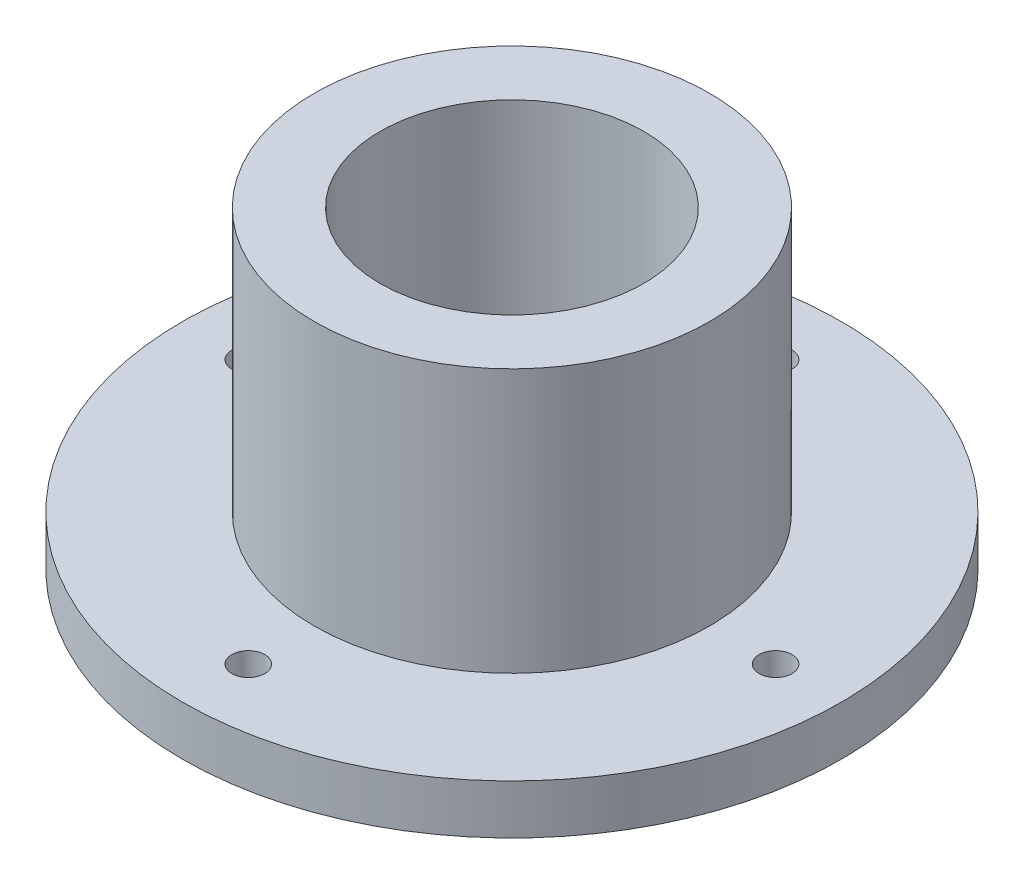
SolidWorks part; units mm, degrees
material "Delrin 2700 NC010, Low Viscosity Acetal Copolymer (SS)"
ref_plane "Front Plane" through (0, 0, 0) normal (0, 0, 1) x (1, 0, 0)
ref_plane "Top Plane" through (0, 0, 0) normal (0, 1, 0) x (1, 0, 0)
ref_plane "Right Plane" through (0, 0, 0) normal (1, 0, 0) x (0, 0, -1)
sketch "Sketch2" plane through (0, 0, 0) normal (0, 1, 0) x (1, 0, 0)
  circle A0 centre (0, 0) radius 63.5
  circle A1 centre (0, 0) radius 38.1
  circle A2 centre (0, 0) radius 25.4
extrude "Boss-Extrude1" add sketch "Sketch2" against normal blind 9.525 contours A0
extrude "Boss-Extrude2" add sketch "Sketch2<3>" along normal blind 50.8 contours A1
sketch "Sketch2<3>" plane through (0, 0, 0) normal (0, 1, 0) x (1, 0, 0) same geometry as "Sketch2"
extrude "Cut-Extrude1" cut sketch "Sketch2<4>" along direction (0, 1, 0) on the side against the normal blind 50.8 and the other way blind 50.8 contours A2
sketch "Sketch2<4>" plane through (0, 0, 0) normal (0, 1, 0) x (1, 0, 0) same geometry as "Sketch2"
sketch "Sketch3" plane through (0, -9.525, 0) normal (0, -1, 0) x (-1, 0, 0)
  circle A0 centre (0, 0) radius 50.8
  circle A1 centre (0, -50.8) radius 3.175
  circle A2 centre (-50.8, 0) radius 3.175
  circle A3 centre (0, 50.8) radius 3.175
  circle A4 centre (50.8, 0) radius 3.175
extrude "Cut-Extrude2" cut sketch "Sketch3" along direction (0, 1, 0) on the side against the normal blind 50.8 contours A2 | A1 | A4 | A3
